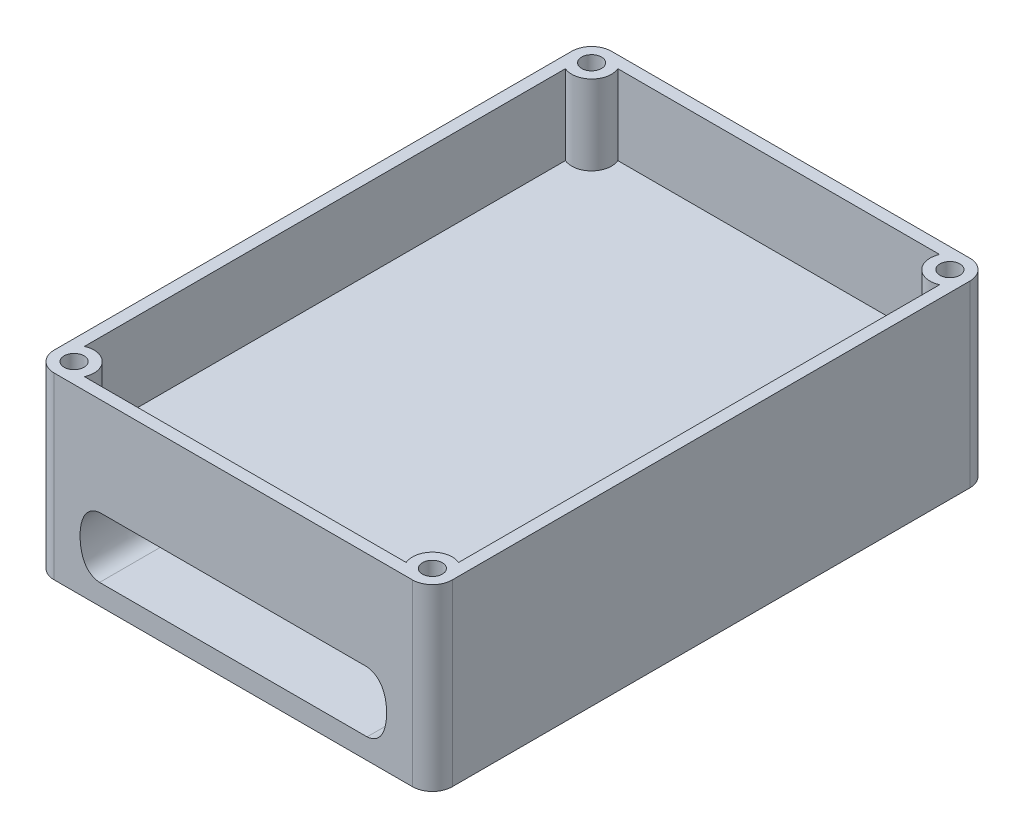
SolidWorks part; units mm, degrees
ref_plane "Front Plane" through (0, 0, 0) normal (0, 0, 1) x (1, 0, 0)
ref_plane "Top Plane" through (0, 0, 0) normal (0, 1, 0) x (1, 0, 0)
ref_plane "Right Plane" through (0, 0, 0) normal (1, 0, 0) x (0, 0, -1)
sketch "Sketch1" plane through (0, 0, 0) normal (0, 1, 0) x (1, 0, 0)
  line L0 (-40.4174, 67) -> (40.4174, 67)
  line L1 (-45, 70) -> (45, 70)
  line L2 (-50, 65) -> (-50, -65)
  line L3 (-45, -70) -> (45, -70)
  line L4 (50, 65) -> (50, -65)
  line L5 (-50, 70) -> (50, -70) construction
  line L6 (-50, -70) -> (50, 70) construction
  line L7 (-46.5164, -67) -> (-46.5, -67)
  line L8 (-47, -60.4174) -> (-47, 60.4174)
  line L11 (-42.5425, -60.6456) -> (42.5425, 60.6456) construction
  line L12 (-42.5425, 60.6456) -> (42.5425, -60.6456) construction
  line L13 (47, -60.4174) -> (47, 60.4174)
  line L14 (-40.4174, -67) -> (40.4174, -67)
  arc A0 (-50, -65) -> (-45, -70) centre (-45, -65) ccw
  arc A1 (45, -70) -> (50, -65) centre (45, -65) ccw
  arc A2 (45, 70) -> (50, 65) centre (45, 65) cw
  arc A3 (-45, 70) -> (-50, 65) centre (-45, 65) ccw
  circle A4 centre (-45, 65) radius 2.5
  circle A5 centre (45, 65) radius 2.5
  circle A6 centre (45, -65) radius 2.5
  circle A7 centre (-45, -65) radius 2.5
  arc A8 (-45, 70) -> (-50, 65) centre (-45, 65) ccw
  arc A9 (40.4174, 67) -> (47, 60.4174) centre (45, 65) ccw
  arc A10 (47, -60.4174) -> (40.4174, -67) centre (45, -65) ccw
  arc A11 (-50, -65) -> (-45, -70) centre (-45, -65) ccw
  arc A12 (50, 65) -> (45, 70) centre (45, 65) ccw
  arc A13 (45, -70) -> (50, -65) centre (45, -65) ccw
  arc A14 (-40.4174, -67) -> (-47, -60.4174) centre (-45, -65) ccw
  arc A15 (-47, 60.4174) -> (-40.4174, 67) centre (-45, 65) ccw
  point P0 (0, 0)
  point P29 (0, 0)
  dimension "D3" = 5
  dimension "D4" = 5
  dimension "D1" = 140
  dimension "outerWidth" = 100
extrude "Boss-Extrude2" add sketch "Sketch1" along normal blind 25 contours L1 A3 L2 A0 L3 A1 L4 A2 A6 A5 A4 A7 L8 A15 L0 A9 L13 A10 L14 A14 | A15 L8 A14 L14 A10 L13 A9 L0 | A6 | A7 | A4 | A5 region at (0, 0, 0) region at (0, 0, -68.2795) region at (-45, 0, -65) region at (45, 0, -65) region at (45, 0, 65) region at (-45, 0, 65)
extrude "Boss-Extrude3" add sketch "Sketch1<3>" along normal blind 20 from surface contours L1 A3 L2 A0 L3 A1 L4 A2 A6 A5 A4 A7 L8 A15 L0 A9 L13 A10 L14 A14 region at (0, 0, -68.2795) starting at face at (0, 25, 0)
sketch "Sketch1<3>" plane through (0, 0, 0) normal (0, 1, 0) x (1, 0, 0) same geometry as "Sketch1"
sketch "Sketch2" plane through (0, 0, 70) normal (0, 0, 1) x (1, 0, 0)
  line L0 (-38.5, 12.7641) -> (38.5, 12.8326) construction
  line L1 (-33.6003, 5.1523) -> (33.6003, 5.1523)
  line L3 (-33.6003, 20.3751) -> (33.6003, 20.3751)
  spline S0 degree 3 poles (-33.6003, 20.3751) (-37.2546, 19.9065) (-39.745, 12.8653) (-37.2554, 5.4191) (-33.6003, 5.1523) knots 0 0 0 0 0.5 1 1 1 1
  spline S1 degree 3 poles (33.6003, 20.3751) (37.2546, 19.9065) (39.745, 13.0024) (37.2554, 5.4191) (33.6003, 5.1523) knots 0 0 0 0 0.5 1 1 1 1
  point P0 (0, 5.1523)
  point P1 (0, 12.7983)
  point P2 (0, 0)
  point P3 (0, 0)
  dimension "D1" = 77
  dimension "D2" = 15.2228
extrude "Cut-Extrude1" cut sketch "Sketch2" against normal blind 130
